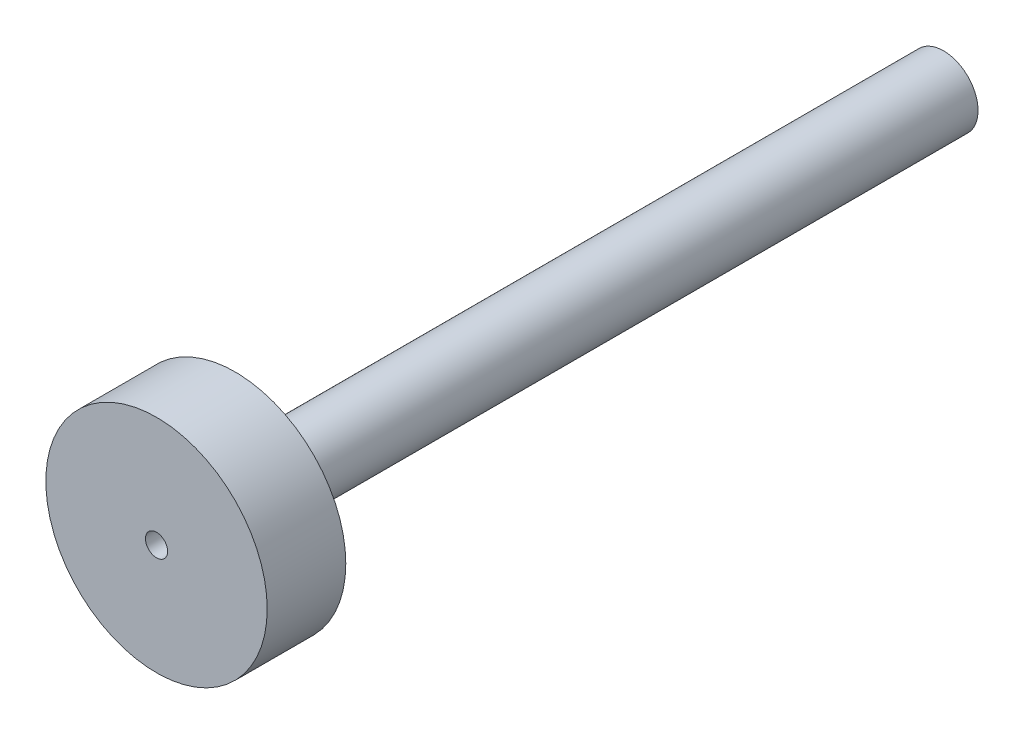
SolidWorks part; units mm, degrees
ref_plane "Front Plane" through (0, 0, 0) normal (0, 0, 1) x (1, 0, 0)
ref_plane "Top Plane" through (0, 0, 0) normal (0, 1, 0) x (1, 0, 0)
ref_plane "Right Plane" through (0, 0, 0) normal (1, 0, 0) x (0, 0, -1)
sketch "Sketch1" plane through (0, 0, 0) normal (0, 0, 1) x (1, 0, 0)
  circle A0 centre (0, 0) radius 12.5
  dimension "D1" = 25
extrude "Boss-Extrude1" add sketch "Sketch1" along normal blind 8.875
sketch "Sketch2" plane through (0, 0, 0) normal (0, 0, -1) x (-1, 0, 0)
  circle A0 centre (0, 0) radius 3.9
  dimension "D1" = 7.8
extrude "Boss-Extrude2" add sketch "Sketch2" along normal blind 80
sketch "Sketch3" plane through (0, 0, 8.875) normal (0, 0, 1) x (1, 0, 0)
  circle A0 centre (0, 0) radius 1.25
  dimension "D1" = 2.5
extrude "Cut-Extrude1" cut sketch "Sketch3" against normal blind 3
